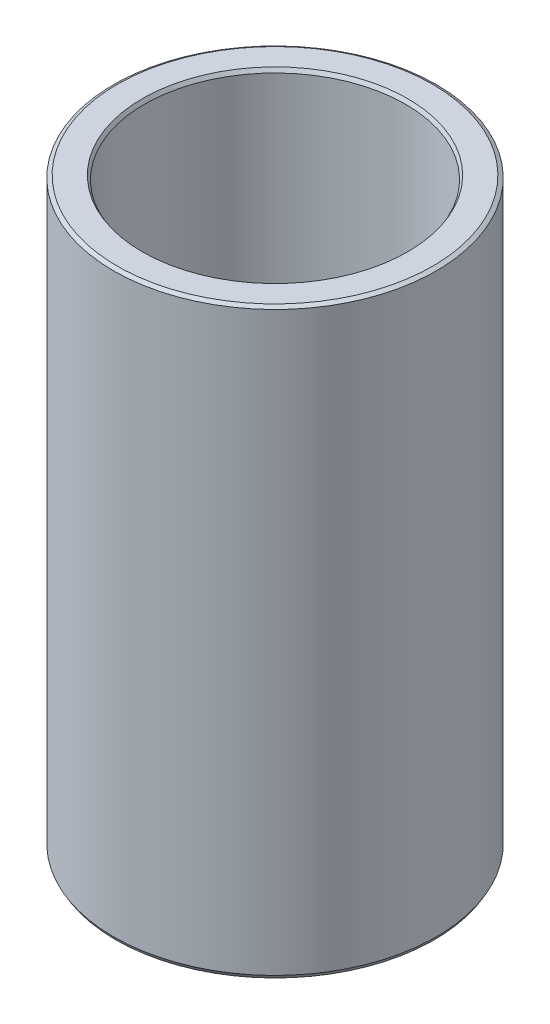
SolidWorks part; units mm, degrees
ref_plane "Front Plane" through (0, 0, 0) normal (0, 0, 1) x (1, 0, 0)
ref_plane "Top Plane" through (0, 0, 0) normal (0, 1, 0) x (1, 0, 0)
ref_plane "Right Plane" through (0, 0, 0) normal (1, 0, 0) x (0, 0, -1)
sketch "Sketch1" plane through (0, 0, 0) normal (0, 1, 0) x (1, 0, 0)
  circle A0 centre (0, 0) radius 40
  dimension "SLEEVE_OD" = 80
extrude "Boss-Extrude1" add sketch "Sketch1" along normal blind 144.4179
sketch "Sketch2" plane through (0, 0, 0) normal (0, 1, 0) x (1, 0, 0)
  circle A0 centre (0, 0) radius 32.3561
  dimension "BORE_D" = 64.7121
extrude "Cut-Extrude1" cut sketch "Sketch2" along normal through all
chamfer "Chamfer1" distance 0.5366 angle 60 4 edges at (0, 144.4179, 32.3561) (0, 0, 32.3561) (0, 0, 40) (0, 144.4179, 40) first distance on face at (0, 144.4179, 32.3561) first distance on face at (0, 0, 32.3561) first distance on face at (0, 144.4179, 40)
